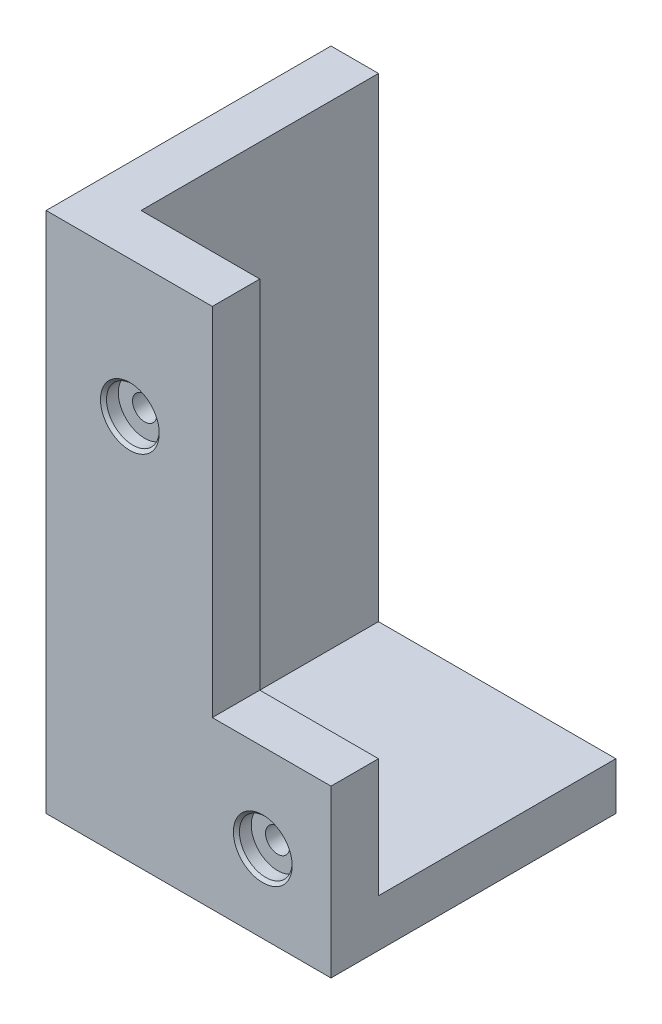
SolidWorks part; units mm, degrees
ref_plane "Front Plane" through (0, 0, 0) normal (0, 0, 1) x (1, 0, 0)
ref_plane "Top Plane" through (0, 0, 0) normal (0, 1, 0) x (1, 0, 0)
ref_plane "Right Plane" through (0, 0, 0) normal (1, 0, 0) x (0, 0, -1)
sketch "Sketch1" plane through (0, 0, 0) normal (0, 0, 1) x (1, 0, 0)
  line L0 (0, 110) -> (10, 110)
  line L1 (0, 0) -> (60, 0)
  line L2 (0, 0) -> (0, 110)
  line L3 (60, 10) -> (60, 0)
  line L5 (10, 110) -> (10, 10)
  line L6 (10, 10) -> (60, 10)
  dimension "D1" = 110
extrude "Boss-Extrude1" add sketch "Sketch1" along normal blind 50
sketch "Sketch2" plane through (0, 0, 50) normal (0, 0, 1) x (1, 0, 0)
  line L0 (0, 110) -> (35, 110)
  line L1 (0, 110) -> (0, 0) construction
  line L2 (10, 110) -> (0, 110) construction
  line L3 (35, 110) -> (35, 35)
  line L4 (35, 35) -> (60, 35)
  line L5 (60, 35) -> (60, 0)
  line L6 (60, 0) -> (60, 10) construction
  line L7 (60, 0) -> (0, 0)
  line L8 (0, 0) -> (0, 110)
  dimension "D1" = 35
  dimension "D2" = 35
extrude "Boss-Extrude2" add sketch "Sketch2" along normal blind 10
hole_wizard "CBORE for #10 Binding Head Machine Screw1" positions "Sketch4" profile "Sketch3" counterbore size "#10" standard "ANSI Inch" end condition through all
sketch "Sketch4" plane through (0, 0, 60) normal (0, 0, 1) x (1, 0, 0)
  point P0 (17.6352, 81.2462)
  point P2 (45.6311, 16.389)
sketch "Sketch3" plane through (17.6352, 81.2462, 60) normal (1, 0, 0) x (0, -1, 0)
  line L0 (0, 0) -> (0, 60)
  line L1 (0, 60) -> (2.5527, 60)
  line L3 (2.5527, 60) -> (2.5527, 3.1242)
  line L4 (5.5562, 3.1242) -> (2.5527, 3.1242)
  line L5 (5.5562, 3.1242) -> (5.5563, 0.635)
  line L6 (5.5563, 0.635) -> (6.1912, 0)
  line L7 (6.1912, 0) -> (0, 0)
  line L8 (-5.5563, 0.635) -> (-6.1912, 0) construction
  line L11 (0, -6.35) -> (0, 107.95) construction
  dimension "Thru Hole Dia." = 5.1054
  dimension "Thru Hole Depth" = 60
  dimension "C'Bore Dia." = 11.1125
  dimension "C'Bore Depth" = 3.1242
  dimension "Near C'Sink Dia." = 12.3825
  dimension "Near C'Sink Angle" = 90
hole_wizard "CBORE for #10 Binding Head Machine Screw2" positions "Sketch6" profile "Sketch5" counterbore size "#10" standard "ANSI Inch" end condition through all
sketch "Sketch6" plane through (0, 0, 0) normal (-1, 0, 0) x (0, 0, 1)
  point P0 (29.5325, 80.1287)
  point P2 (29.5325, 30.5727)
sketch "Sketch5" plane through (0, 80.1287, 29.5325) normal (0, 1, 0) x (0, 0, 1)
  line L0 (0, 0) -> (0, 60.0001)
  line L1 (0, 60.0001) -> (2.5527, 60.0001)
  line L3 (2.5527, 60.0001) -> (2.5527, 3.1242)
  line L4 (5.5562, 3.1242) -> (2.5527, 3.1242)
  line L5 (5.5562, 3.1242) -> (5.5563, 0.635)
  line L6 (5.5563, 0.635) -> (6.1912, 0)
  line L7 (6.1912, 0) -> (0, 0)
  line L8 (-5.5563, 0.635) -> (-6.1912, 0) construction
  line L11 (0, -6.35) -> (0, 107.95) construction
  dimension "Thru Hole Dia." = 5.1054
  dimension "Thru Hole Depth" = 60.0001
  dimension "C'Bore Dia." = 11.1125
  dimension "C'Bore Depth" = 3.1242
  dimension "Near C'Sink Dia." = 12.3825
  dimension "Near C'Sink Angle" = 90
hole_wizard "CBORE for #10 Binding Head Machine Screw3" positions "Sketch8" profile "Sketch7" counterbore size "#10" standard "ANSI Inch" end condition through all
sketch "Sketch8" plane through (0, 0, 0) normal (0, -1, 0) x (-1, 0, 0)
  point P0 (-30.1275, -29.9362)
sketch "Sketch7" plane through (30.1275, 0, 29.9362) normal (1, 0, 0) x (0, 0, -1)
  line L0 (0, 0) -> (0, 110.0001)
  line L1 (0, 110.0001) -> (2.5527, 110.0001)
  line L3 (2.5527, 110.0001) -> (2.5527, 3.1242)
  line L4 (5.5562, 3.1242) -> (2.5527, 3.1242)
  line L5 (5.5562, 3.1242) -> (5.5562, 0.635)
  line L6 (5.5562, 0.635) -> (6.1912, 0)
  line L7 (6.1912, 0) -> (0, 0)
  line L8 (-5.5562, 0.635) -> (-6.1912, 0) construction
  line L11 (0, -6.35) -> (0, 107.95) construction
  dimension "Thru Hole Dia." = 5.1054
  dimension "Thru Hole Depth" = 110.0001
  dimension "C'Bore Dia." = 11.1125
  dimension "C'Bore Depth" = 3.1242
  dimension "Near C'Sink Dia." = 12.3825
  dimension "Near C'Sink Angle" = 90
